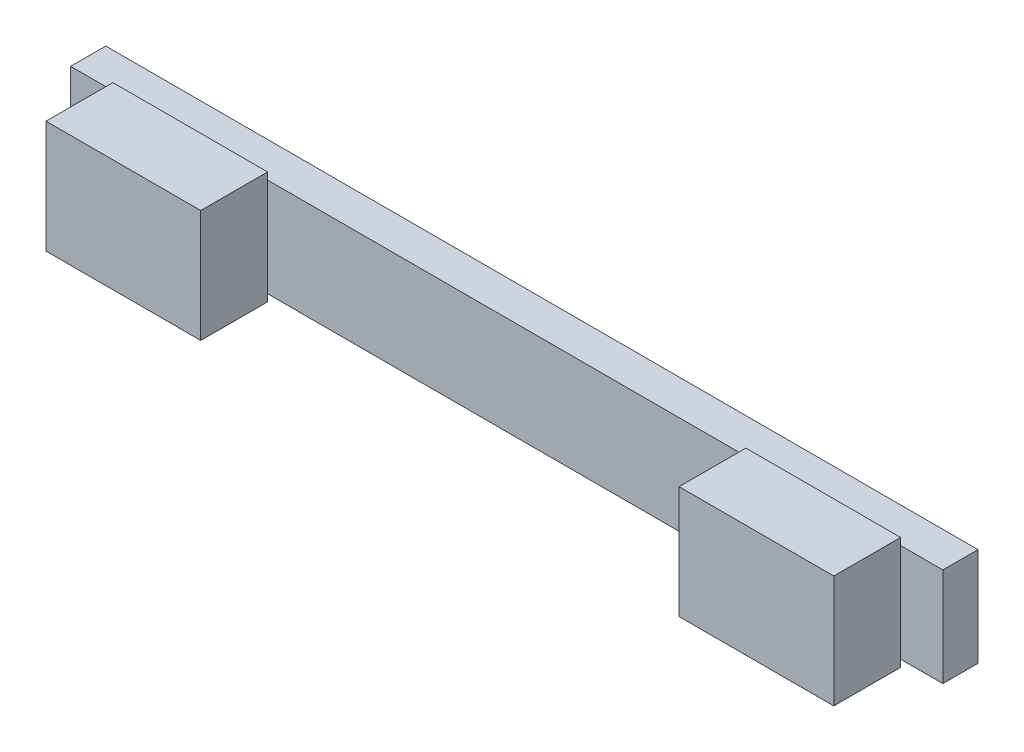
SolidWorks part; units mm, degrees
material "AISI Type 316L stainless steel"
ref_plane "Front Plane" through (0, 0, 0) normal (0, 0, 1) x (1, 0, 0)
ref_plane "Top Plane" through (0, 0, 0) normal (0, 1, 0) x (1, 0, 0)
ref_plane "Right Plane" through (0, 0, 0) normal (1, 0, 0) x (0, 0, -1)
sketch "Extrude sketch 1" plane through (0, 0, 0) normal (0, 0, 1) x (1, 0, 0)
  line L0 (178, -7) -> (302, -7)
  line L1 (302, -7) -> (302, 7)
  line L2 (302, 7) -> (178, 7)
  line L3 (178, 7) -> (178, -7)
  dimension "D1" = 124
  dimension "D2" = 14
extrude "Extrude 1" add sketch "Extrude sketch 1" along normal blind 5 from offset 356 separate body offset against normal yes
sketch "Extrude sketch 2" plane through (0, 0, 0) normal (0, 0, 1) x (1, 0, 0)
  line L0 (274, -8) -> (296, -8)
  line L1 (296, -8) -> (296, 8)
  line L2 (296, 8) -> (274, 8)
  line L3 (274, 8) -> (274, -8)
  dimension "D1" = 22
  dimension "D2" = 16
extrude "Extrude 2" add sketch "Extrude sketch 2" along normal blind 9.5 from offset 351 separate body offset against normal yes
sketch "Extrude sketch 3" plane through (0, 0, 0) normal (0, 0, 1) x (1, 0, 0)
  line L0 (184, -8) -> (206, -8)
  line L1 (206, -8) -> (206, 8)
  line L2 (206, 8) -> (184, 8)
  line L3 (184, 8) -> (184, -8)
  dimension "D1" = 22
  dimension "D2" = 16
extrude "Extrude 3" add sketch "Extrude sketch 3" along normal blind 9.5 from offset 351 separate body offset against normal yes
combine bodies "Combine (weld / assembly of features)" operation type add bodies to combine 101 102 103
